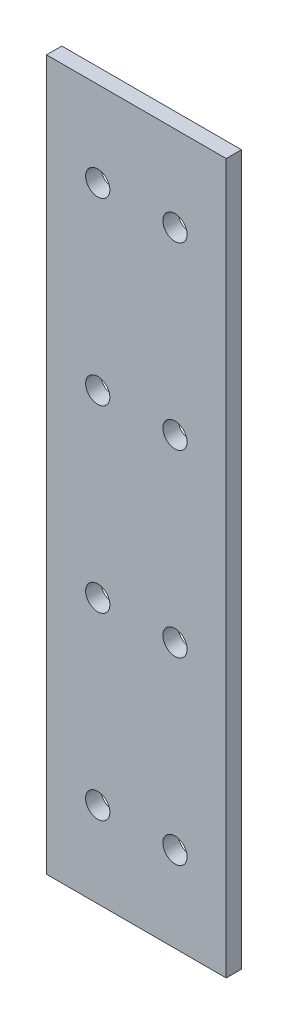
SolidWorks part; units mm, degrees
material "ABS"
ref_plane "Front Plane" through (0, 0, 0) normal (0, 0, 1) x (1, 0, 0)
ref_plane "Top Plane" through (0, 0, 0) normal (0, 1, 0) x (1, 0, 0)
ref_plane "Right Plane" through (0, 0, 0) normal (1, 0, 0) x (0, 0, -1)
sketch "Sketch1" plane through (0, 0, 0) normal (0, 0, 1) x (1, 0, 0)
  line L1 (-10, -39.5) -> (10, -39.5)
  line L2 (-10, -39.5) -> (-10, 39.5)
  line L3 (-10, 39.5) -> (10, 39.5)
  line L4 (10, -39.5) -> (10, 39.5)
  line L5 (-10, -39.5) -> (10, 39.5) construction
  line L6 (-10, 39.5) -> (10, -39.5) construction
  point P0 (0, 0)
  dimension "D1" = 20
  dimension "D2" = 79
extrude "Boss-Extrude1" add sketch "Sketch1" along normal blind 1.7
sketch "Sketch3" plane through (0, 0, 1.7) normal (0, 0, 1) x (1, 0, 0)
  line L0 (0, 0) -> (0, 39.5) construction
  line L1 (10, 39.5) -> (-10, 39.5) construction
  line L2 (0, 0) -> (-4.3, -10) construction
  line L3 (-4.3, 10) -> (0, 0) construction
  circle A0 centre (-4.3, 30) radius 1.35
  circle A1 centre (-4.3, 10) radius 1.35
  circle A2 centre (-4.3, -10) radius 1.35
  circle A3 centre (-4.3, -30) radius 1.35
  circle A4 centre (4.3, -30) radius 1.35
  circle A5 centre (4.3, -10) radius 1.35
  circle A6 centre (4.3, 10) radius 1.35
  circle A7 centre (4.3, 30) radius 1.35
  dimension "D1" = 2.7
  dimension "D2" = 4.3
  dimension "D4" = 20
  dimension "D3" = 4
extrude "Cut-Extrude1" cut sketch "Sketch3" against normal through all
equation "\"smallPulleyTeeth\"= 30"
equation "\"largePulleyTeeth\"= 30"
equation "\"eighthThick\"= 3.0mm"
equation "\"sixteenthThick\" = 1.7mm"
equation "\"quarterThick\"=6.0mm"
equation "\"OD\" = 145mm"
equation "\"puckAngle\" = 60.5deg"
equation "\"puckDiam\" = 76.5mm"
equation "\"puckDist\" = 85mm"
equation "\"scoopFillet\" = 5mm"
equation "\"axlePress\" = 5.9mm"
equation "\"press\" = 0.2mm"
equation "\"wheelClear\" = 0.3mm"
equation "\"10-32clear\" = 4.8mm"
equation "\"10-32tap\" = 4.45mm"
equation "\"6-32clear\" = 3.3mm"
equation "\"8-32clear\" = 4.0mm"
equation "\"4-40clear\" = 3.0mm"
equation "\"wheelHeight\" = 22mm"
equation "\"wheelWell\" = 65mm"
equation "\"ledSmall\" = 3.1mm"
equation "\"ledLarge\" = 4.2mm"
equation "\"ledLength\" = 4.2mm"
equation "\"4-40close\" = 2.7mm"
equation "\"4-40nutThick\" = 2.2mm"
equation "\"4-40nutWidth\" = 6.2mm"
equation "\"4-40insertHeight\" = 3.5mm"
equation "\"4-40insert\" = 4.25mm"
equation "\"D1@Boss-Extrude1\"=\"sixteenthThick\""
equation "\"D1@Sketch3\"=\"4-40close\""
